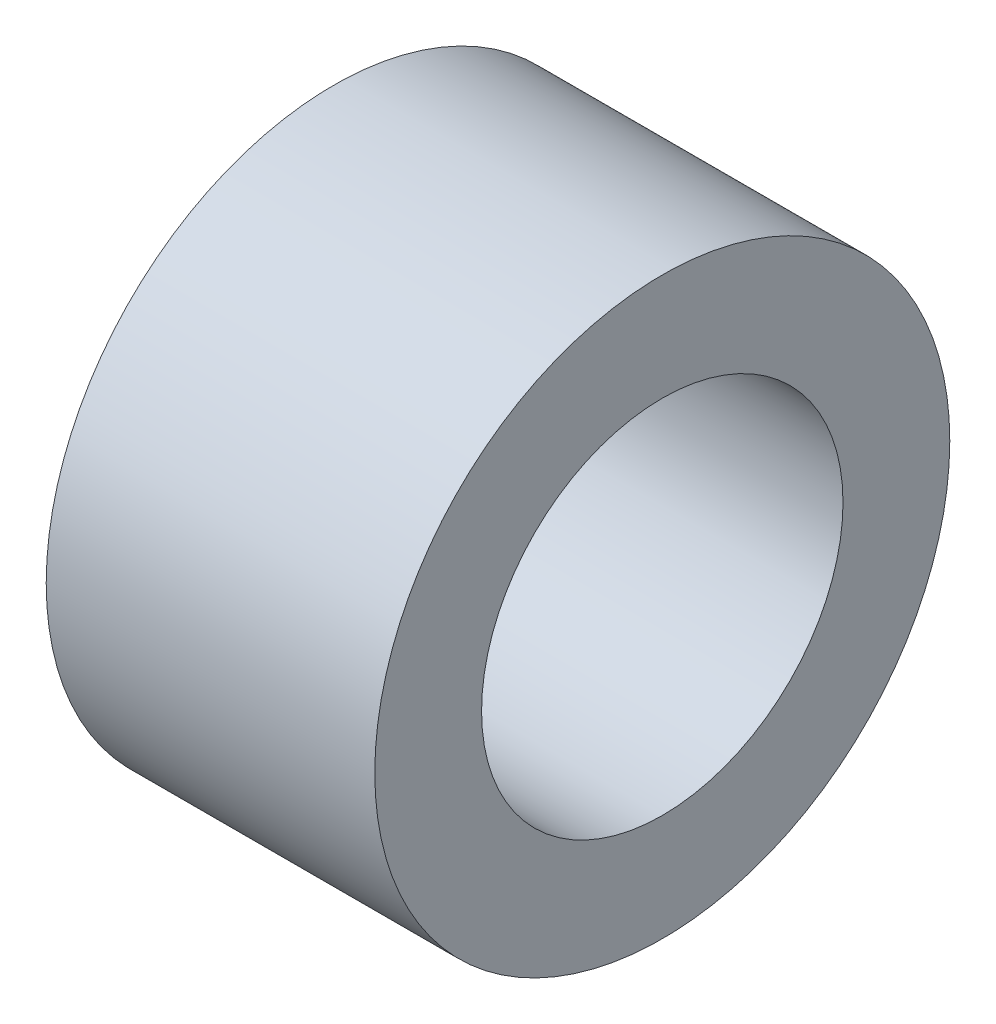
SolidWorks part; units mm, degrees
material "ABS"
ref_plane "Front Plane" through (0, 0, 0) normal (0, 0, 1) x (1, 0, 0)
ref_plane "Top Plane" through (0, 0, 0) normal (0, 1, 0) x (1, 0, 0)
ref_plane "Right Plane" through (0, 0, 0) normal (1, 0, 0) x (0, 0, -1)
sketch "Sketch1" plane through (0, 0, 0) normal (1, 0, 0) x (0, 0, -1)
  circle A0 centre (0, 0) radius 2.794
  circle A1 centre (0, 0) radius 4.445
  dimension "D1" = 5.588
  dimension "D2" = 8.89
extrude "Boss-Extrude1" add sketch "Sketch1" along normal blind 5.08 contours A1 A0 region at (0, 0, 4.3193)
